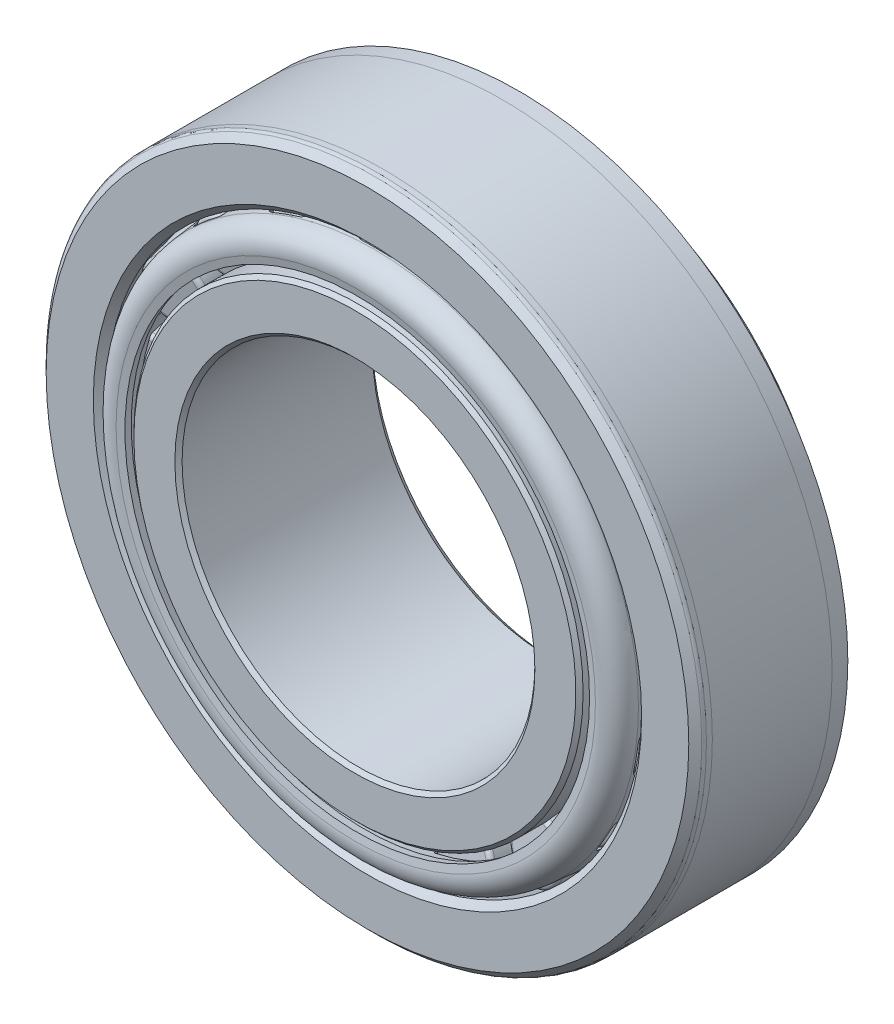
SolidWorks part; units mm, degrees
ref_plane "Front Plane" through (0, 0, 0) normal (0, 0, 1) x (1, 0, 0)
ref_plane "Top Plane" through (0, 0, 0) normal (0, 1, 0) x (1, 0, 0)
ref_plane "Right Plane" through (0, 0, 0) normal (1, 0, 0) x (0, 0, -1)
sketch "Sketch1" plane through (0, 0, 0) normal (1, 0, 0) x (0, 0, -1)
  line L0 (-9.525, 41.4734) -> (-9.525, 33.55)
  line L1 (-9.525, 33.55) -> (9.525, 37.81)
  line L2 (9.525, 37.81) -> (9.525, 41.4734)
  line L3 (9.525, 41.4734) -> (-9.525, 41.4734)
  line L4 (0, 0) -> (10110.1541, 0) construction
  line L5 (-0.0394, 35.6712) -> (7.9375, 0) construction
  line L6 (14.2875, 31.545) -> (14.2875, 22.225)
  line L7 (14.2875, 22.225) -> (-11.1125, 22.225)
  line L8 (-11.1125, 22.225) -> (-11.1125, 28.3)
  line L9 (-11.1125, 28.3) -> (-7.4923, 28.3)
  line L10 (14.2875, 31.545) -> (9.7764, 31.545)
  line L12 (14.2875, 41.4734) -> (-11.1125, 41.4734) construction
  line L14 (-11.1125, 30.7715) -> (13.835, 35.7201)
  line L15 (13.835, 35.7201) -> (14.0335, 34.7196)
  line L16 (14.0335, 34.7196) -> (-9.9135, 29.9695)
  line L17 (-9.9135, 29.9695) -> (-9.8143, 29.4692)
  line L18 (-8.5758, 33.7623) -> (8.5758, 37.5977) construction
  line L19 (-11.1125, 30.7715) -> (-10.8148, 29.2708)
  line L20 (-10.8148, 29.2708) -> (-9.8143, 29.4692)
  line L21 (8.5758, 37.5977) -> (10.1848, 29.4858)
  line L22 (10.1848, 29.4858) -> (-7.1321, 26.4841)
  line L23 (-7.1321, 26.4841) -> (-8.5758, 33.7623)
  line L25 (-7.8539, 30.1232) -> (9.3803, 33.5418) construction
  line L27 (0, 35.68) -> (0.7632, 31.8325) construction
  line L28 (0.7632, 31.8325) -> (1.5264, 27.9849) construction
  line L29 (-11.1125, 41.4734) -> (-11.1125, 30.7715) construction
  point P7 (0, 41.4734)
  point P44 (9.3317, 33.787)
  dimension "Width" = 19.05
  dimension "Inner Ring Width" = 25.4
  dimension "Effective Center" = 6.35
  dimension "Width A" = 23.8125
  dimension "Cone Thick" = 1.02
  dimension "D17" = 0.51
  dimension "Roller S Diameter" = 7.42
  dimension "Roller L Diameter" = 8.27
  dimension "Roller Length" = 17.57
  dimension "D2" = 0.25
  dimension "Back Cone Dim" = 0.254
  dimension "Diameter B" = 67.1
  dimension "Diameter C" = 56.6
  dimension "Diameter F" = 75.62
  dimension "Diameter E" = 63.09
  dimension "D3" = 25.4
  dimension "ID" = 44.45
  dimension "OD" = 82.9469
  dimension "Cage Width" = 25.4
sketch "Sketch0" plane through (0, 0, 0) normal (0, 0, 1) x (1, 0, 0)
  circle A0 centre (0, 0) radius 22.225
  circle A1 centre (0, 0) radius 41.4734
  dimension "D1" = 82.9469
  dimension "D2" = 44.45
sketch "Sketch2" plane through (0, 0, 0) normal (1, 0, 0) x (0, 0, -1)
  line L0 (-9.525, 41.4734) -> (-9.525, 33.55)
  line L1 (-9.525, 33.55) -> (9.525, 37.81)
  line L2 (9.525, 37.81) -> (9.525, 41.4734)
  line L3 (9.525, 41.4734) -> (-9.525, 41.4734)
revolve "Revolve1" add sketch "Sketch2" angle 360 about L4
sketch "Sketch3" plane through (0, 0, 0) normal (1, 0, 0) x (0, 0, -1)
  line L0 (-11.1125, 28.3) -> (-11.1125, 22.225)
  line L1 (-11.1125, 22.225) -> (14.2875, 22.225)
  line L2 (14.2875, 22.225) -> (14.2875, 31.545)
  line L3 (14.2875, 31.545) -> (9.7764, 31.545)
  line L4 (9.7764, 31.545) -> (10.1848, 29.4858)
  line L5 (10.1848, 29.4858) -> (-7.1321, 26.4841)
  line L6 (-7.1321, 26.4841) -> (-7.4923, 28.3)
  line L7 (-7.4923, 28.3) -> (-11.1125, 28.3)
revolve "Revolve2" add sketch "Sketch3" angle 360 about L4
sketch "Sketch4" plane through (0, 0, 0) normal (1, 0, 0) x (0, 0, -1)
  line L0 (14.0335, 34.7196) -> (13.835, 35.7201)
  line L1 (13.835, 35.7201) -> (-11.5574, 33.0146)
  line L2 (-11.5574, 33.0146) -> (-10.8148, 29.2708)
  line L3 (-10.8148, 29.2708) -> (-9.8143, 29.4692)
  line L4 (-9.8143, 29.4692) -> (-9.9135, 29.9695)
  line L5 (-9.9135, 29.9695) -> (14.0335, 34.7196)
  line L6 (-8.5758, 33.7623) -> (-11.1125, 30.7715) construction
  line L7 (-9.8441, 32.2669) -> (-8.5758, 33.7623) construction
  point P14 (-9.2099, 33.0146)
revolve "Revolve3" add sketch "Sketch4" angle 360 about L4
sketch "Sketch6" plane through (0, 0, 0) normal (1, 0, 0) x (0, 0, -1)
  line L0 (10.1848, 29.4858) -> (9.3803, 33.5418)
  line L1 (9.3803, 33.5418) -> (-7.8539, 30.1232)
  line L3 (-7.8539, 30.1232) -> (-7.1321, 26.4841)
  line L4 (-7.1321, 26.4841) -> (10.1848, 29.4858)
  line L5 (-7.8539, 30.1232) -> (9.3803, 33.5418) construction
  line L6 (-7.1321, 26.4841) -> (-8.5758, 33.7623) construction
revolve "Revolve4" add sketch "Sketch6" angle 360 about L25
sketch "Sketch8" plane through (0, 3.06, -15.4267) normal (0, 0.1946, -0.9809) x (-1, 0, 0)
  line L0 (0, 26.9406) -> (0, 31.0756) construction
  circle A0 centre (0, 31.0756) radius 2.0675
  point P3 (0, 29.0081)
extrude "Cut-Extrude1" cut sketch "Sketch8" against normal blind 0.635
fillet "Fillet7" radius 0.9525 1 edges at (0, 35.4462, -8.3552)
chamfer "Chamfer4" distance 0.5169 angle 45 1 edges at (0, 29.4858, -10.1848)
fillet "Fillet8" radius 0.5565 1 edges at (0, 26.4841, 7.1321)
pattern_circular "CirPattern1" count 18 over 360 about axis through (0, 0, 0) along (0, 0, 1) of "Revolve4"
fillet "Fillet9" radius 2.625 1 edges at (33.0146, 0, 11.5574)
fillet "Fillet10" radius 0.3315 2 edges at (35.7201, 0, -13.835) (34.7196, 0, -14.0335)
sketch "Sketch9" plane through (0, 0, 0) normal (1, 0, 0) x (0, 0, -1)
  line L0 (-7.8539, 30.1232) -> (9.3803, 33.5418)
  line L1 (9.3803, 33.5418) -> (10.239, 29.2128)
  line L2 (10.239, 29.2128) -> (-7.0779, 26.2111)
  line L3 (-7.0779, 26.2111) -> (-7.8539, 30.1232)
  line L4 (-7.1321, 26.4841) -> (10.1848, 29.4858) construction
  dimension "D1" = 0.2783
revolve "Cut-Revolve2" cut sketch "Sketch9" angle 360 about L0
fillet "Fillet11" radius 0.371 4 edges at (-3.5673, 31.8726, 8.2009) (3.5673, 31.8726, 8.2009) (4.3541, 34.2486, -9.2401) (-4.3541, 34.2486, -9.2401)
pattern_circular "CirPattern2" count 18 over 360 about axis through (0, 0, 0) along (0, 0, 1) of "Cut-Revolve2", "Fillet11"
chamfer "Chamfer1" distance 0.9904 angle 45 2 edges at (41.4734, 0, 9.525) (33.55, 0, 9.525)
ref_plane "Plane1" through (0, 0, 7.5441) normal (0, 0, 1) x (1, 0, 0)
ref_plane "Plane2" through (0, 0, -7.5441) normal (0, 0, -1) x (-1, 0, 0)
split line "Split Line1"
split line "Split Line2"
fillet "Fillet6" radius 0.5943 1 edges at (-41.4734, 0, 8.5346)
chamfer "Chamfer2" distance 0.4556 angle 45 2 edges at (28.3, 0, 11.1125) (22.225, 0, 11.1125)
chamfer "Chamfer3" distance 0.932 angle 45 2 edges at (22.225, 0, -14.2875) (31.545, 0, -14.2875)
sketch "Sketch7" plane through (0, 0, 0) normal (1, 0, 0) x (0, 0, -1)
  line L0 (14.2875, 31.545) -> (14.2875, 22.225) construction
  line L1 (-11.1125, 28.3) -> (-7.4923, 28.3) construction
  line L2 (-11.1125, 22.225) -> (-11.1125, 28.3) construction
  line L3 (14.2875, 22.225) -> (-11.1125, 22.225) construction
  line L4 (14.2875, 31.545) -> (9.7764, 31.545) construction
  line L5 (10.1848, 29.4858) -> (-7.1321, 26.4841) construction
  line L6 (8.5758, 37.5977) -> (10.1848, 29.4858) construction
  line L7 (-9.525, 33.55) -> (9.525, 37.81) construction
  line L8 (-7.1321, 26.4841) -> (-8.5758, 33.7623) construction
  line L9 (14.2875, 31.545) -> (14.2875, 22.225)
  line L10 (-11.1125, 28.3) -> (-7.4923, 28.3)
  line L11 (-11.1125, 22.225) -> (-11.1125, 28.3)
  line L12 (14.2875, 22.225) -> (-11.1125, 22.225)
  line L13 (14.2875, 31.545) -> (9.7764, 31.545)
  line L14 (10.1848, 29.4858) -> (-7.1321, 26.4841)
  line L15 (8.5758, 37.5977) -> (10.1848, 29.4858)
  line L16 (-8.5758, 33.7623) -> (8.5758, 37.5977)
  line L17 (-7.1321, 26.4841) -> (-8.5758, 33.7623)
  line L18 (0, 0) -> (14.2875, 0) construction
  line L21 (-7.1321, -26.4841) -> (-8.5758, -33.7623)
  line L22 (-8.5758, -33.7623) -> (8.5758, -37.5977)
  line L23 (8.5758, -37.5977) -> (10.1848, -29.4858)
  line L24 (10.1848, -29.4858) -> (-7.1321, -26.4841)
  line L25 (14.2875, -31.545) -> (9.7764, -31.545)
  line L26 (14.2875, -22.225) -> (-11.1125, -22.225)
  line L27 (-11.1125, -22.225) -> (-11.1125, -28.3)
  line L28 (-11.1125, -28.3) -> (-7.4923, -28.3)
  line L29 (14.2875, -31.545) -> (14.2875, -22.225)
equation "\"D17@Sketch1\" = \"Cone Thick@Sketch1\" / 2"
equation "\"D1@Chamfer1\"=(\"OD@Sketch1\"-\"Diameter B@Sketch1\")*0.5*0.125"
equation "\"D1@Plane1\"=(\"OD@Sketch1\"-\"Diameter B@Sketch1\")*0.5*0.25"
equation "\"D1@Plane2\"=(\"OD@Sketch1\"-\"Diameter B@Sketch1\")*0.5*0.25"
equation "\"D1@Fillet6\"=(\"OD@Sketch1\"-\"Diameter B@Sketch1\")*0.5*0.075"
equation "\"D1@Chamfer2\"=(\"Diameter C@Sketch1\"-\"ID@Sketch1\")*0.5*0.075"
equation "\"D1@Chamfer3\"=(\"Diameter E@Sketch1\"-\"ID@Sketch1\")*0.5*0.1"
equation "\"D1@Chamfer4\"=\"Roller L Diameter@Sketch1\"*0.0625"
equation "\"D1@Fillet8\"=\"Roller S Diameter@Sketch1\"*0.075"
equation "\"D1@Fillet9\"=(\"Diameter B@Sketch1\"-\"Diameter C@Sketch1\")*0.5*0.5"
equation "\"D1@Fillet10\"=\"Cone Thick@Sketch1\"*0.325"
equation "\"D1@Sketch9\"=\"Roller S Diameter@Sketch1\"*0.0375"
equation "\"D1@Fillet11\"=\"Roller S Diameter@Sketch1\"*0.05"
equation "\"D1@CirPattern2\"=\"Number of Rollers@CirPattern1\""
